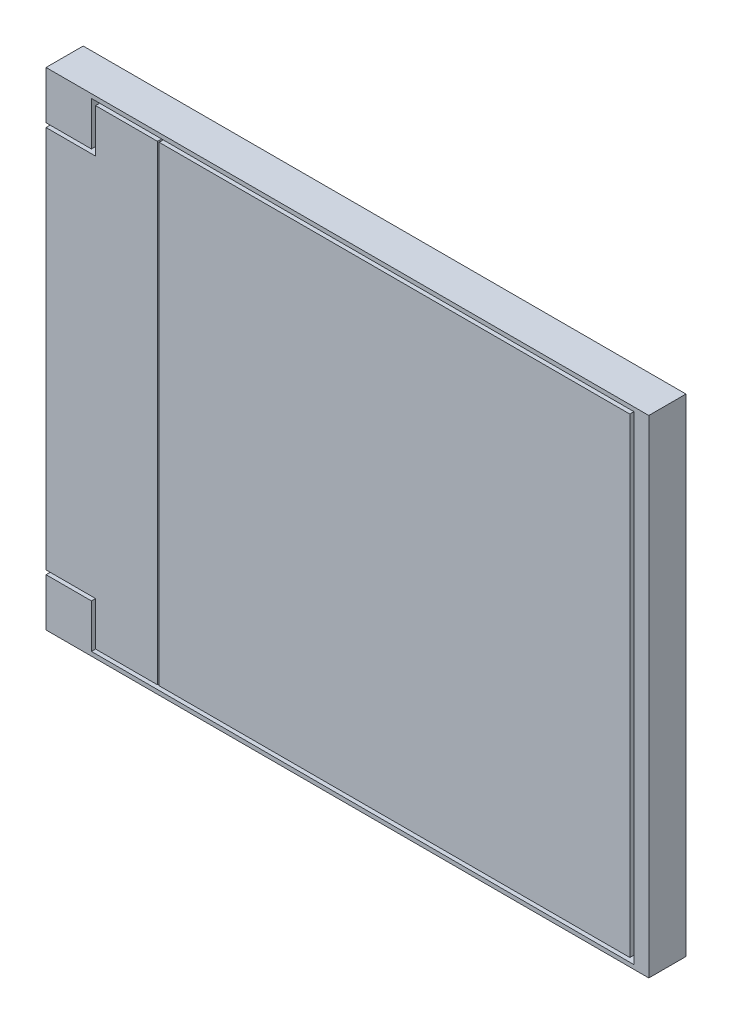
SolidWorks part; units mm, degrees
ref_plane "前视基准面" through (0, 0, 0) normal (0, 0, 1) x (1, 0, 0)
ref_plane "上视基准面" through (0, 0, 0) normal (0, 1, 0) x (1, 0, 0)
ref_plane "右视基准面" through (0, 0, 0) normal (1, 0, 0) x (0, 0, -1)
sketch "底面草图" plane through (0, 0, 0) normal (0, 0, 1) x (1, 0, 0)
  line L0 (0, 29.5) -> (0, 0)
  line L1 (0, 0) -> (36.5, 0)
  line L3 (0, 29.5) -> (36.5, 29.5)
  line L4 (36.5, 0) -> (36.5, 29.5)
  line L5 (0, 26.6) -> (2.75, 26.6)
  line L11 (0, 2.9) -> (2.75, 2.9)
  line L18 (2.75, 0.25) -> (35.6, 0.25)
  line L23 (2.75, 0.25) -> (2.75, 29.25)
  line L24 (2.75, 29.25) -> (35.6, 29.25)
  line L25 (35.6, 0.25) -> (35.6, 29.25)
  point P5 (18.25, 14.75)
  point P14 (19.175, 14.75)
extrude "外框" add sketch "底面草图" along normal blind 2.25 contours L4 L3 | L0 L1 region at (18.25, 29.4531, 0)
extrude "底面" add sketch "底面草图<3>" along normal blind 0.1 contours L18 L25 L24 L23 | L11 L23 L5 L0 region at (1.375, 14.75, 0) region at (19.175, 14.75, 0)
sketch "底面草图<3>" plane through (0, 0, 0) normal (0, 0, 1) x (1, 0, 0) same geometry as "底面草图"
sketch "屏幕草图" plane through (0, 0, 0.1) normal (0, 0, 1) x (1, 0, 0)
  line L4 (35.35, 29) -> (35.35, 0.5)
  line L5 (35.35, 0.5) -> (6.85, 0.5)
  line L6 (6.85, 0.5) -> (6.85, 29)
  line L7 (6.85, 29) -> (35.35, 29)
  line L9 (6.75, 29) -> (6.75, 0.5)
  line L10 (3, 26.35) -> (3, 29)
  line L13 (3, 0.5) -> (6.75, 0.5)
  line L14 (3, 0.5) -> (3, 3.15)
  line L15 (3, 29) -> (6.75, 29)
  line L19 (3, 3.15) -> (0, 3.15)
  line L20 (0, 26.6) -> (0, 2.9) construction
  line L21 (0, 3.15) -> (0, 26.35)
  line L22 (0, 26.35) -> (3, 26.35)
  line M12 (0, 26.6) -> (0, 2.9)
extrude "屏幕" add sketch "屏幕草图" along normal up to surface (2.15 mm away) contours L7 L6 L5 L4 | L22 L19 L14 L13 L9 L15 L10 M12 region at (21.1, 14.75, 0.1) region at (3.5439, 14.75, 0.1) up to face at (12.9333, 14.75, 2.25)
sketch "背面触点草图" plane through (0, 0, 0) normal (0, 0, -1) x (-1, 0, 0)
  line L0 (-7.3, 9.35) -> (-7.3, 9.75)
  line L1 (0, 29.5) -> (0, 0) construction
  line L2 (0, 25.5) -> (-8.8, 25.5)
  line L3 (0, 4) -> (-8.8, 4)
  line L4 (-7.3, 9.75) -> (-8.8, 9.75)
  line L5 (-7.3, 19.75) -> (-8.8, 19.75)
  line L6 (-8.8, 4) -> (-8.8, 25.5)
  line L7 (0, 25.5) -> (0, 4)
  line L8 (-7.3, 20.15) -> (-7.3, 19.75)
  line L9 (-7.3, 9.35) -> (-8.8, 9.35)
  line L10 (-7.3, 20.15) -> (-8.8, 20.15)
extrude "背部触点" add sketch "背面触点草图" along normal blind 0.01 contours L9 L0 L4 L6 | L8 L10 L6 L5 region at (8.05, 9.55, 0) region at (8.05, 19.95, 0)
